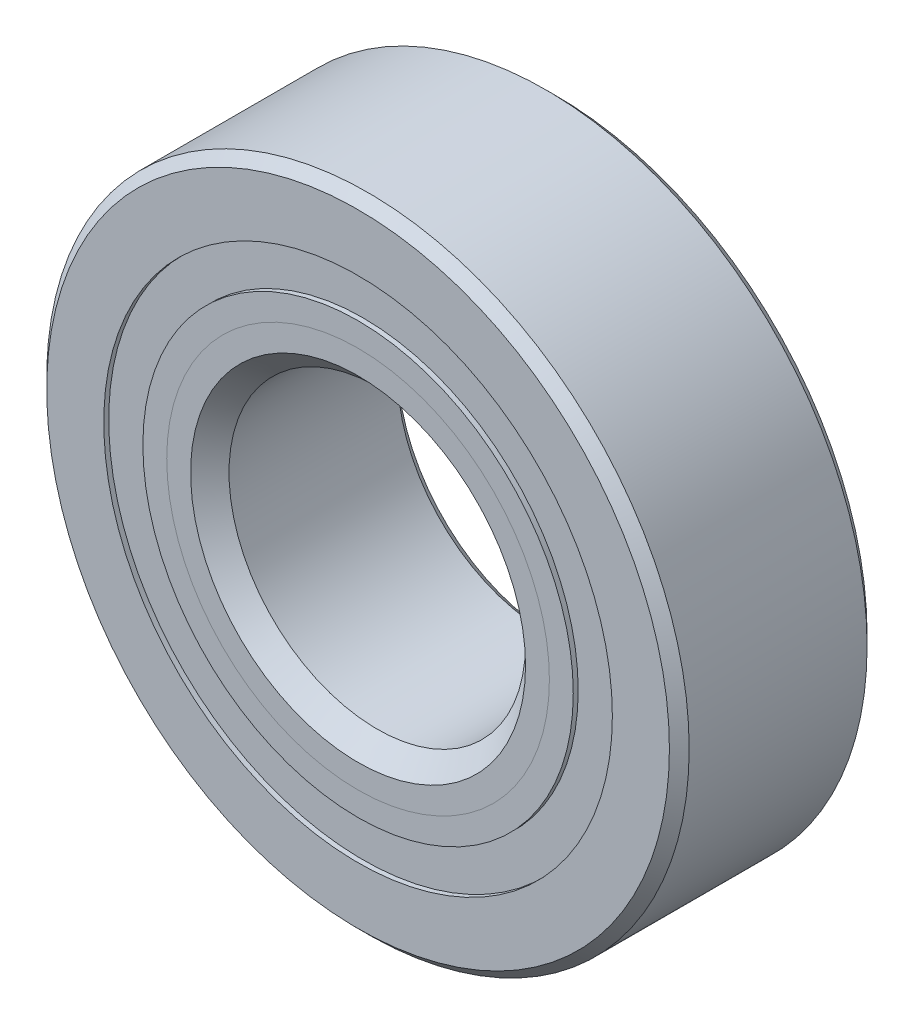
SolidWorks part; units mm, degrees
ref_plane "Front Plane" through (0, 0, 0) normal (0, 0, 1) x (1, 0, 0)
ref_plane "Top Plane" through (0, 0, 0) normal (0, 1, 0) x (1, 0, 0)
ref_plane "Right Plane" through (0, 0, 0) normal (1, 0, 0) x (0, 0, -1)
sketch "Sketch1" plane through (0, 0, 0) normal (1, 0, 0) x (0, 0, -1)
  line L0 (-6.35, 0) -> (6.35, 0) construction
  line L1 (0, 20.6375) -> (0, -20.6375) construction
  line L2 (5.715, 20.6375) -> (-5.715, 20.6375)
  line L3 (-5.715, 20.6375) -> (-6.35, 20.0025)
  line L4 (-6.35, 20.0025) -> (-6.35, 16.3373)
  line L5 (-6.35, 16.3373) -> (-2.8222, 16.3373)
  line L6 (6.35, 16.3373) -> (2.8222, 16.3373)
  line L7 (6.35, 20.0025) -> (6.35, 16.3373)
  line L8 (5.715, 20.6375) -> (6.35, 20.0025)
  line L9 (0, 20.6375) -> (0, 15.0813) construction
  line L10 (0, 15.0813) -> (0, 9.525) construction
  arc A0 (-2.8222, 16.3373) -> (2.8222, 16.3373) centre (0, 15.0813) cw
  point P14 (0, 9.525)
  dimension "Width" = 12.7
  dimension "OD" = 41.275
  dimension "D1" = 45
  dimension "D2" = 0.635
  dimension "Shaft Dia" = 19.05
  dimension "D3" = 5.6444
  dimension "D4" = 1.256
revolve "Revolve1" add sketch "Sketch1" angle 360 about L0
sketch "Sketch2" plane through (0, 0, 0) normal (1, 0, 0) x (0, 0, -1)
  line L0 (-6.35, 13.8252) -> (-2.8222, 13.8252)
  line L1 (-6.35, 20.0025) -> (-6.35, -20.0025) construction
  line L2 (-6.35, 13.8252) -> (-6.35, 12.2919)
  line L3 (-6.35, 12.2919) -> (-4.8167, 10.7586)
  line L4 (-4.8167, 10.7586) -> (0, 10.7586)
  line L5 (0, 20.6375) -> (0, -20.6375) construction
  line L6 (0, 10.7586) -> (0, 11.9921)
  line L7 (0, 11.9921) -> (0, 9.525) construction
  line L8 (-6.35, 13.8252) -> (-6.35, 10.7586) construction
  line L9 (-6.35, 10.7586) -> (-4.8167, 10.7586) construction
  arc A0 (-2.8222, 13.8252) -> (0, 11.9921) centre (0, 15.0813) ccw
  arc A1 (2.8222, 16.3373) -> (-2.8222, 16.3373) centre (0, 15.0813) ccw construction
  circle A2 centre (0, 15.0813) radius 3.0891 construction
  dimension "D1" = 45
revolve "Revolve2" add sketch "Sketch2" angle 360 about L0
sketch "Sketch3" plane through (0, 0, 0) normal (1, 0, 0) x (0, 0, -1)
  line L0 (-6.35, 12.2919) -> (-4.8167, 10.7586)
  line L1 (-4.8167, 10.7586) -> (0, 10.7586)
  line L2 (0, 10.7586) -> (0, 11.9921)
  line L3 (-6.35, 12.2919) -> (-6.35, 10.7586)
  line L4 (-6.35, 13.8252) -> (-6.35, 10.7586) construction
  line L5 (-6.35, 10.7586) -> (-5.1164, 9.525)
  line L6 (-5.1164, 9.525) -> (5.715, 9.525)
  line L7 (5.715, 20.6375) -> (5.715, -20.6375) construction
  line L8 (5.715, 9.525) -> (6.35, 10.16)
  line L9 (6.35, -20.0025) -> (6.35, 20.0025) construction
  line L10 (6.35, 10.16) -> (6.35, 13.8252)
  line L11 (6.35, 13.8252) -> (2.8222, 13.8252)
  line L13 (5.715, 20.6375) -> (6.35, 20.0025) construction
  circle A0 centre (0, 15.0813) radius 3.0891 construction
  arc A1 (2.8222, 13.8252) -> (0, 11.9921) centre (0, 15.0813) cw
revolve "Revolve3" add sketch "Sketch3" angle 360 about L0
sketch "Sketch4" plane through (0, 0, 0) normal (1, 0, 0) x (0, 0, -1)
  line L0 (-3.0891, 15.0813) -> (3.0891, 15.0813)
  circle A1 centre (0, 15.0813) radius 3.0891 construction
  arc A2 (-3.0891, 15.0813) -> (3.0891, 15.0813) centre (0, 15.0813) cw
  arc A3 (2.8222, 16.3373) -> (-2.8222, 16.3373) centre (0, 15.0813) ccw construction
revolve "Revolve4" add sketch "Sketch4" angle 360 about L0
ref_axis "Axis1" through (0, 0, -6.35) along (0, 0, 1)
pattern_circular "CirPattern1" count 14 every 25.714 about axis through (0, 0, -6.35) along (0, 0, 1) of bodies 104
sketch "Sketch5" plane through (0, 0, 0) normal (1, 0, 0) x (0, 0, -1)
  line L0 (-6.35, 16.3373) -> (-2.8222, 16.3373) construction
  line L1 (-6.0325, 16.3373) -> (-3.0891, 16.3373)
  line L2 (-6.0325, 16.3373) -> (-6.0325, 13.8252)
  line L3 (-6.0325, 13.8252) -> (-3.0891, 13.8252)
  line L4 (-3.0891, 16.3373) -> (-3.0891, 13.8252)
  line L5 (-6.35, 13.8252) -> (-2.8222, 13.8252) construction
  line L6 (-5.715, 20.6375) -> (-6.35, 20.0025) construction
  line L7 (0, 20.6375) -> (0, 9.525) construction
  line L8 (6.0325, 13.8252) -> (3.0891, 13.8252)
  line L9 (3.0891, 16.3373) -> (3.0891, 13.8252)
  line L10 (6.0325, 16.3373) -> (3.0891, 16.3373)
  line L11 (6.0325, 16.3373) -> (6.0325, 13.8252)
  circle A0 centre (0, 15.0813) radius 3.0891 construction
  point P10 (-6.0325, 20.32)
revolve "Revolve5" add sketch "Sketch5" angle 360 about L0
equation "\"D2@Sketch1\" = \"Width@Sketch1\"*.05"
equation "\"D3@Sketch1\" = \"Width@Sketch1\"/2.25"
equation "\"D4@Sketch1\" = (((\"OD@Sketch1\"-\"Width@Sketch1\")/2)/3.25)/3.5"
equation "\"D2@CirPattern1\" = 360/\"Balls@CirPattern1\""
